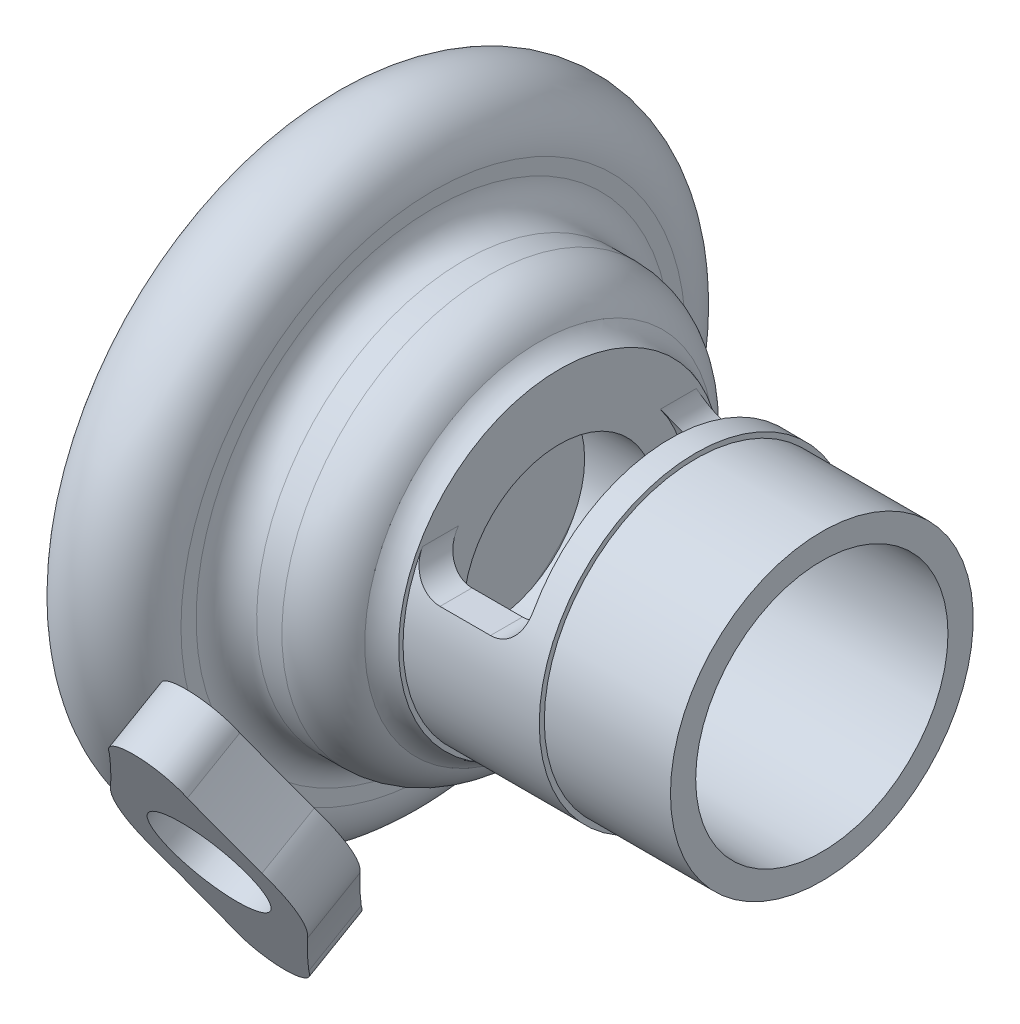
SolidWorks part; units mm, degrees
ref_plane "Front Plane" through (0, 0, 0) normal (0, 0, 1) x (1, 0, 0)
ref_plane "Top Plane" through (0, 0, 0) normal (0, 1, 0) x (1, 0, 0)
ref_plane "Right Plane" through (0, 0, 0) normal (1, 0, 0) x (0, 0, -1)
sketch "Sketch1" plane through (0, 0, 0) normal (0, 0, 1) x (1, 0, 0)
  line L0 (-49, 0) -> (49, 0) construction
  line L1 (49, 0) -> (49, 25) construction
  line L2 (49, 25) -> (19, 25)
  line L3 (19, 25) -> (19, 31)
  line L4 (19, 31) -> (24, 31)
  line L5 (24, 31) -> (24, 30)
  line L6 (24, 30) -> (49, 30)
  line L7 (49, 30) -> (49, 25)
revolve "Revolve1" add sketch "Sketch1" angle 360 about L0
sketch "Sketch3" plane through (19, 0, 0) normal (-1, 0, 0) x (0, 0, 1)
  circle A1 centre (0, 0) radius 31
  circle A2 centre (0, 0) radius 31
  circle A3 centre (0, 0) radius 25
  circle A4 centre (0, 0) radius 31
  circle M2 centre (0, 0) radius 25
  circle M3 centre (0, 0) radius 31
  dimension "D1" = 0
extrude "Boss-Extrude1" add sketch "Sketch3" along normal blind 22 contours M3 M2 region at (19, 0, -30.1232)
sketch "Sketch4" plane through (0, 0, 0) normal (0, 0, 1) x (1, 0, 0)
  line L0 (-3, 31) -> (19, 31)
  line L1 (24, 31) -> (-3, 31) construction
  line L2 (-3, 31) -> (-3, 15)
  line L3 (-3, 31) -> (-3, -31) construction
  line L4 (3, 9) -> (13, 9)
  line L5 (19, 15) -> (19, 31)
  arc A0 (13, 9) -> (19, 15) centre (13, 15) ccw
  arc A1 (3, 9) -> (-3, 15) centre (3, 15) cw
  point P13 (-3, 9)
  dimension "D1" = 6
extrude "Cut-Extrude1" cut sketch "Sketch4" against normal through all both and the other way through all
sketch "Sketch10" plane through (0, 0, 0) normal (0, 0, 1) x (1, 0, 0)
  line L0 (49, 30) -> (49, 10.2608) construction
  line L1 (49, -30) -> (49, 30) construction
  line L2 (49, 30) -> (49, -30) construction
  line L3 (49, 0) -> (-60.8461, 0) construction
  line L4 (-3, 19) -> (-3, 31.8677)
  line L5 (-28, 0) -> (-25, 0)
  line L7 (-17, 38.0042) -> (-17, 38)
  line L8 (-25, 30) -> (-25, 0)
  line L9 (-28, 30) -> (-28, 0)
  line L10 (-17, 22) -> (-17, 19)
  line L12 (-17, 19) -> (-3, 19)
  arc A0 (-17, 22) -> (-25, 30) centre (-17, 30) ccw
  arc A1 (-7.0011, 34.585) -> (-28, 30) centre (-17, 30) ccw
  arc A2 (-7.0011, 34.585) -> (-3, 31.8677) centre (-1.3458, 38.6078) ccw
  dimension "D1" = 8
revolve "Revolve2" add sketch "Sketch10" angle 360 about L3
sketch "Sketch11" plane through (0, 0, 0) normal (1, 0, 0) x (0, 0, -1)
  line L0 (0, 0) -> (-16.9842, 0) construction
  line L1 (0, 0) -> (-55.4256, -32)
  dimension "D1" = 64
  dimension "D2" = 210
ref_plane "Plane5" through (0, -32, 55.4256) normal (0, -0.5, 0.866) x (1, 0, 0)
sketch "Sketch12" plane through (0, -32, 55.4256) normal (0, -0.5, 0.866) x (1, 0, 0)
  line L2 (-17, 0) -> (-17, -17.5) construction
  line L4 (-17, 0) -> (-17, 44.3251) construction
  arc A0 (-9.2709, 24.0642) -> (-24.7291, 24.0642) centre (-17, 22) ccw
  arc A1 (-2.0099, 9.0304) -> (-2.0099, -9.0304) centre (-17, 0) cw
  circle A2 centre (-17, 0) radius 11
  arc A3 (-31.9901, 9.0304) -> (-24.7291, 24.0642) centre (-285.7816, 140.8758) ccw
  arc A4 (-2.0099, 9.0304) -> (-9.2709, 24.0642) centre (251.7816, 140.8758) cw
  arc A5 (-31.9901, 9.0304) -> (-31.9901, -9.0304) centre (-17, 0) ccw
  arc A6 (-2.0099, -9.0304) -> (-9.2709, -24.0642) centre (251.7816, -140.8758) ccw
  arc A7 (-31.9901, -9.0304) -> (-24.7291, -24.0642) centre (-285.7816, -140.8758) cw
  arc A8 (-9.2709, -24.0642) -> (-24.7291, -24.0642) centre (-17, -22) cw
extrude "Boss-Extrude2" add sketch "Sketch12" against normal blind 12 separate body
sketch "Sketch14" plane through (0, 0, 0) normal (0, 0, 1) x (1, 0, 0)
  line L0 (-28, 0) -> (-52, 0) construction
  line L1 (-28, 30) -> (-28, -30) construction
  line L2 (-52, 38) -> (-47, 38)
  line L3 (-52, 38) -> (-52, 50)
  line L4 (-47, 38) -> (-47, 50)
  line L5 (-47, 50) -> (-39, 50) construction
  line L6 (-31, 50) -> (-31, 19)
  line L7 (-28, 50) -> (-28, 47)
  line L8 (-17, 41) -> (-22, 41)
  line L9 (-52, 50) -> (-51.4097, 50)
  line L10 (-28, 30) -> (-28, 21)
  line L11 (-31, 19) -> (-30, 19)
  arc A0 (-31, 50) -> (-47, 50) centre (-39, 50) ccw
  arc A2 (-51.4097, 50) -> (-49.9205, 51.32) centre (-51.4097, 51.5) ccw
  arc A3 (-28, 50) -> (-49.9205, 51.32) centre (-39, 50) ccw
  arc A4 (-22, 41) -> (-28, 47) centre (-22, 47) cw
  arc A5 (-30, 19) -> (-28, 21) centre (-30, 21) ccw
  arc A6 (-7.0011, 34.585) -> (-28, 30) centre (-17, 30) ccw construction
  arc A7 (-17, 41) -> (-28, 30) centre (-17, 30) ccw
  dimension "D1" = 6
  dimension "D2" = 1.5
  dimension "D3" = 2
revolve "Revolve3" add sketch "Sketch14" angle 360 about L0
sketch "Sketch15" plane through (0, 0, 0) normal (0, 1, 0) x (1, 0, 0)
  circle A0 centre (8, 0) radius 6
extrude "Cut-Extrude2" cut sketch "Sketch15" against normal up to next
